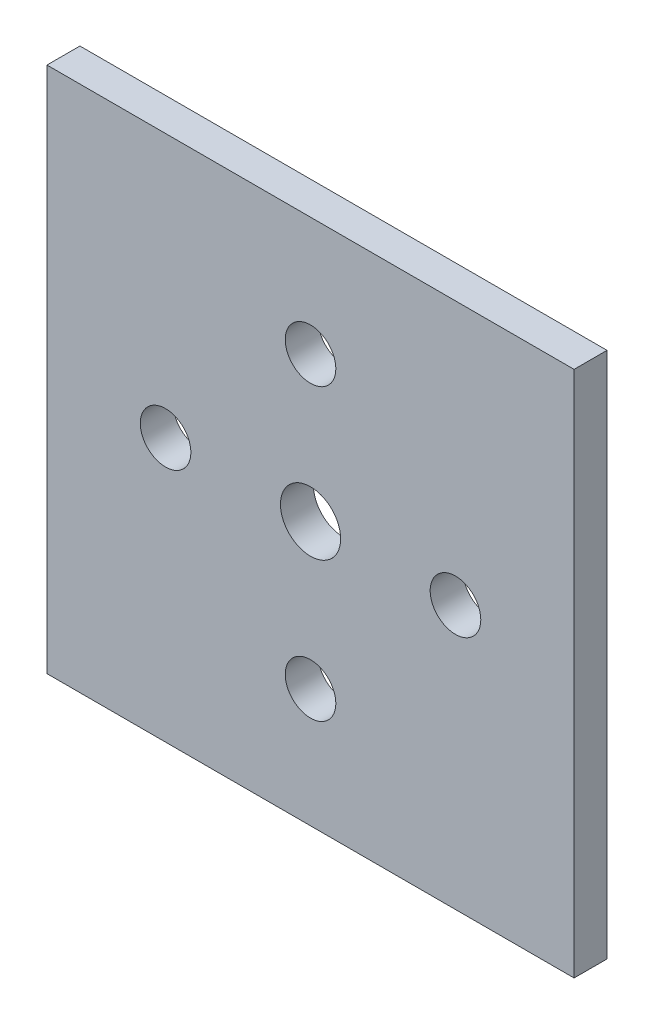
SolidWorks part; units mm, degrees
material "6061-T6 (SS)"
ref_plane "Front Plane" through (0, 0, 0) normal (0, 0, 1) x (1, 0, 0)
ref_plane "Top Plane" through (0, 0, 0) normal (0, 1, 0) x (1, 0, 0)
ref_plane "Right Plane" through (0, 0, 0) normal (1, 0, 0) x (0, 0, -1)
sketch "Sketch1" plane through (0, 0, 0) normal (0, 0, 1) x (1, 0, 0)
  line L1 (0, 0) -> (25.4, 0)
  line L2 (0, 0) -> (0, 25.4)
  line L3 (0, 25.4) -> (25.4, 25.4)
  line L4 (25.4, 0) -> (25.4, 25.4)
  dimension "D1" = 25.4
  dimension "D2" = 25.4
base flange "Base-Flange1" sketch "Sketch1" thickness 1.5875 reverse thickness direction no parameters "D1"=254
sketch "Sketch6" plane through (0, 0, 0) normal (0, 0, 1) x (1, 0, 0)
  line L0 (12.7, 25.4) -> (12.7, 12.7) construction
  line L1 (25.4, 25.4) -> (0, 25.4) construction
  dimension "D1" = 12.7
hole_wizard "M2.5 Clearance Hole1" positions "Sketch8" profile "Sketch7" hole size "M2.5" standard "ANSI Metric" end condition through all
sketch "Sketch8" plane through (0, 0, 0) normal (0, 0, 1) x (1, 0, 0)
  point P0 (12.7, 12.7)
sketch "Sketch7" plane through (12.7, 12.7, 0) normal (1, 0, 0) x (0, -1, 0)
  line L0 (0, 0) -> (0, 1.5875)
  line L1 (0, 1.5875) -> (1.45, 1.5875)
  line L2 (1.45, 1.5875) -> (1.45, 0)
  line L5 (1.45, 0) -> (0, 0)
  line L11 (0, -6.35) -> (0, 107.95) construction
  dimension "Thru Hole Dia." = 2.9
  dimension "Thru Hole Depth" = 1.5875
sketch "Sketch9" plane through (0, 0, 0) normal (0, 0, 1) x (1, 0, 0)
  line L0 (12.7, 12.7) -> (19.685, 12.7)
  dimension "D1" = 6.985
hole_wizard "#2 Clearance Hole1" positions "Sketch12" profile "Sketch10" hole size "#2" standard "ANSI Inch" end condition through all
sketch "Sketch12" plane through (0, 0, 0) normal (0, 0, 1) x (1, 0, 0)
  point P0 (19.685, 12.7)
sketch "Sketch10" plane through (19.685, 12.7, 0) normal (1, 0, 0) x (0, -1, 0)
  line L0 (0, 0) -> (0, 1.5875)
  line L1 (0, 1.5875) -> (1.2192, 1.5875)
  line L2 (1.2192, 1.5875) -> (1.2192, 0)
  line L5 (1.2192, 0) -> (0, 0)
  line L11 (0, -6.35) -> (0, 107.95) construction
  dimension "Thru Hole Dia." = 2.4384
  dimension "Thru Hole Depth" = 1.5875
pattern_circular "CirPattern1" count 4 over 360 about axis through (12.7, 12.7, 0) along (0, 0, 1) of "#2 Clearance Hole1"
sketch "Bend-Lines1" [suppressed] plane through (0, 0, 0) normal (0, 1, 0) x (1, 0, 0)
sketch "Bounding-Box1" [suppressed] plane through (0, 0, 0) normal (0, 1, 0) x (1, 0, 0)
sheet metal parameters "Sheet-Metal1" thickness 1.5875 parameters "D1"=254
flat pattern "Flat-Pattern1" [suppressed]
sketch "Bend-Lines2" plane through (0, 0, 0) normal (0, 1, 0) x (1, 0, 0)
sketch3d "Bounding-Box2" [suppressed]
  line L0 (-25.4, 25.4, 0) -> (-25.4, 0, 0) construction
  line L1 (0, 25.4, 0) -> (0, 0, 0) construction
  line L2 (-25.4, 25.4, 0) -> (0, 25.4, 0) construction
  line L3 (-25.4, 0, 0) -> (0, 0, 0) construction
sheet metal parameters "Sheet-Metal2" thickness 1.5875 parameters "D1"=254
flat pattern "Flat-Pattern1"
sketch "Bend-Lines2" plane through (0, 0, 0) normal (0, 1, 0) x (1, 0, 0)
sketch3d "Bounding-Box2" [suppressed]
  line L0 (25.4, 25.4, 0) -> (25.4, 0, 0) construction
  line L1 (0, 25.4, 0) -> (0, 0, 0) construction
  line L2 (25.4, 25.4, 0) -> (0, 25.4, 0) construction
  line L3 (25.4, 0, 0) -> (0, 0, 0) construction
sheet metal parameters "Sheet-Metal3" thickness 1.5875 parameters "D1"=254
flat pattern "Flat-Pattern1"
sketch "Bend-Lines2" plane through (0, 0, 0) normal (0, 1, 0) x (1, 0, 0)
sketch3d "Bounding-Box2" [suppressed]
  line L0 (25.4, 25.4, 0) -> (25.4, 0, 0) construction
  line L1 (0, 25.4, 0) -> (0, 0, 0) construction
  line L2 (25.4, 25.4, 0) -> (0, 25.4, 0) construction
  line L3 (25.4, 0, 0) -> (0, 0, 0) construction
sheet metal parameters "Sheet-Metal4" thickness 1.5875 parameters "D1"=254
flat pattern "Flat-Pattern1"
sketch "Bend-Lines2" plane through (0, 0, 0) normal (0, 1, 0) x (1, 0, 0)
sketch3d "Bounding-Box2" [suppressed]
  line L0 (25.4, 25.4, 0) -> (25.4, 0, 0) construction
  line L1 (0, 25.4, 0) -> (0, 0, 0) construction
  line L2 (25.4, 25.4, 0) -> (0, 25.4, 0) construction
  line L3 (25.4, 0, 0) -> (0, 0, 0) construction
